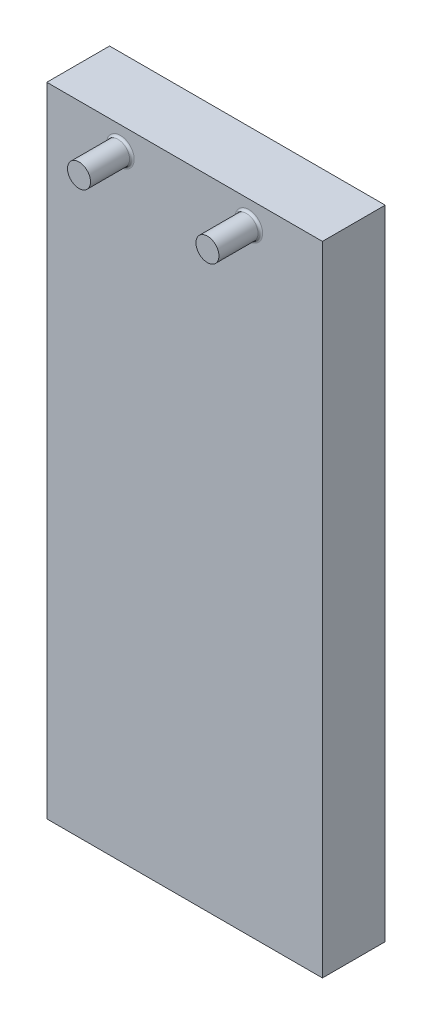
SolidWorks part; units mm, degrees
ref_plane "Front Plane" through (0, 0, 0) normal (0, 0, 1) x (1, 0, 0)
ref_plane "Top Plane" through (0, 0, 0) normal (0, 1, 0) x (1, 0, 0)
ref_plane "Right Plane" through (0, 0, 0) normal (1, 0, 0) x (0, 0, -1)
sketch "Sketch1" plane through (0, 0, 0) normal (0, 1, 0) x (1, 0, 0)
  line L1 (-59.92, -13.65) -> (59.92, -13.65)
  line L2 (-59.92, -13.65) -> (-59.92, 13.65)
  line L3 (-59.92, 13.65) -> (59.92, 13.65)
  line L4 (59.92, -13.65) -> (59.92, 13.65)
  line L5 (-59.92, -13.65) -> (59.92, 13.65) construction
  line L6 (-59.92, 13.65) -> (59.92, -13.65) construction
  point P0 (0, 0)
  dimension "D1" = 119.84
  dimension "D2" = 27.3
extrude "Boss-Extrude1" add sketch "Sketch1" along normal blind 277.37
sketch "Sketch2" plane through (0, 0, 13.65) normal (0, 0, 1) x (1, 0, 0)
  line L0 (-59.92, 257.37) -> (59.92, 257.37)
  line L1 (-59.92, 277.37) -> (-59.92, 0) construction
  line L2 (59.92, 277.37) -> (59.92, 0) construction
  line L3 (-59.92, 277.37) -> (59.92, 277.37) construction
  line L4 (-59.92, 257.37) -> (-59.92, 277.37)
  line L5 (-59.92, 267.37) -> (59.92, 267.37) construction
  circle A2 centre (-27.92, 267.37) radius 5
  circle A3 centre (27.92, 267.37) radius 5
  dimension "D4" = 10
  dimension "D1" = 20
  dimension "D2" = 32
  dimension "D3" = 32
extrude "Boss-Extrude2" add sketch "Sketch2" along normal blind 18 contours L5 A3 | A3 L5 | L5 A2 | A2 L5 region at (-27.92, 269.4921, 13.65) region at (27.92, 269.4921, 13.65) region at (27.92, 265.2479, 13.65) region at (-27.92, 265.2479, 13.65)
fillet "Fillet1" radius 1 2 edges at (22.92, 267.37, 13.65) (-32.92, 267.37, 13.65)
equation "\"PCWidth\"= 340mm'Distance of longest part parallel to GPU(ussually GPU)"
equation "\"PCLength\"= 143mm'Length across I/O from PS to GPU"
equation "\"PCHeight\"= 190mm'Tallest point with mobo laying flat"
equation "\"WallThickness\"= 9mm'Thickness of each outer tank wall"
equation "\"ThermoBarrierThickness\"= 6mm'Thickness of barrier between hot side and cold side"
equation "\"HotSideGap\"= 15mm'Space in the hot side that hot fluid flows into"
equation "\"PCClearance\"= 40mm'Clearance from top of tank to top of PC"
equation "\"RadiatorHeight\"= 277.37mm'Final Height from ground of radiators"
equation "\"D1@Boss-Extrude1\"=\"RadiatorHeight\""
